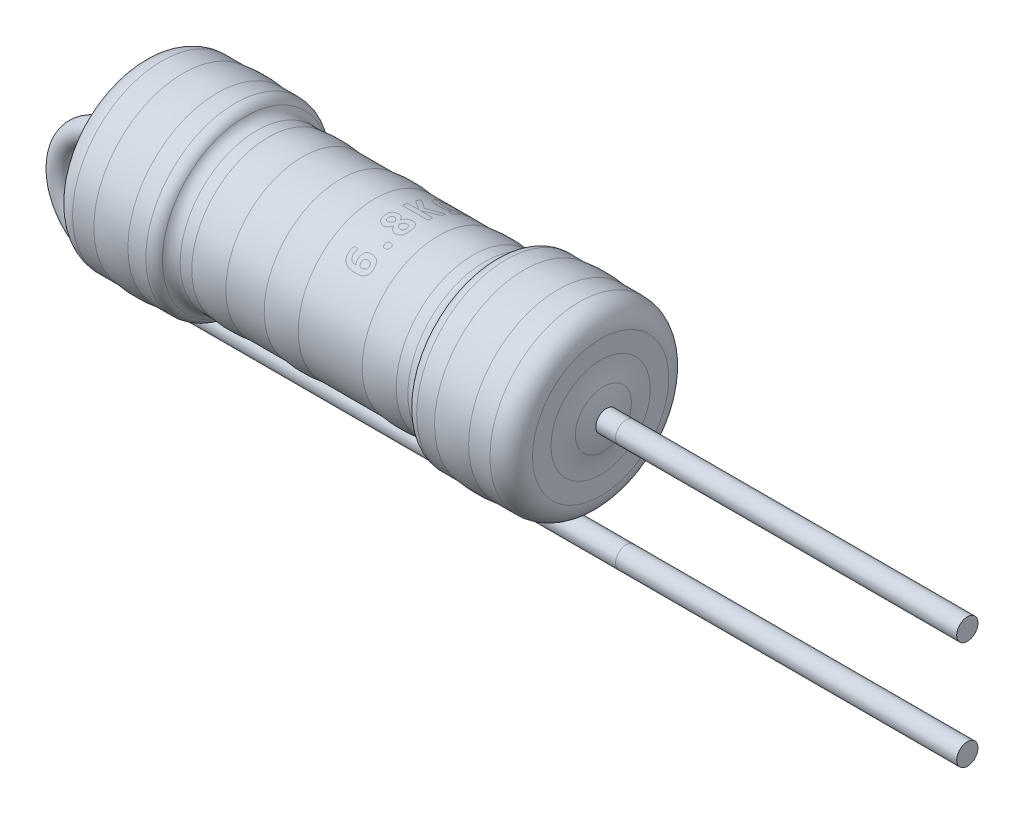
SolidWorks part; units mm, degrees
ref_plane "Front Plane" through (0, 0, 0) normal (0, 0, 1) x (1, 0, 0)
ref_plane "Top Plane" through (0, 0, 0) normal (0, 1, 0) x (1, 0, 0)
ref_plane "Right Plane" through (0, 0, 0) normal (1, 0, 0) x (0, 0, -1)
sketch "Sketch Set Wire Width" plane through (0, 0, 0) normal (0, 0, 1) x (1, 0, 0)
  line L0 (0, 0) -> (6, 0)
  line L1 (6, -2.54) -> (-6, -2.54)
  line L2 (6, 0) -> (14.0102, 0)
  line L3 (-6, 0) -> (-6, -2.54) construction
  line L4 (-6, 0) -> (-6, -2.54) construction
  line L5 (6, -2.54) -> (6, 0) construction
  line L6 (6, -2.54) -> (14.0102, -2.54)
  line L7 (14.0102, -2.54) -> (14.0102, 0) construction
  line L8 (-6, 0) -> (0, 0)
  arc A0 (-6, 0) -> (-6, -2.54) centre (-6, -1.27) ccw
  dimension "D2" = 2.54
  dimension "D3" = 30
  dimension "D1" = 12
  dimension "D4" = 6
sketch "Sketch Wire Diameter" plane through (0, 0, 0) normal (1, 0, 0) x (0, 0, -1)
  circle A0 centre (0, 0) radius 0.25
  dimension "D1" = 0.5
sweep "SET WIRE LENGTH" add profiles "Sketch Wire Diameter" path "Sketch Set Wire Width"
sketch "Sketch3" plane through (0, 0, 0) normal (0, 0, 1) x (1, 0, 0)
  line L0 (-5.4, 0) -> (5.4, 0)
  line L1 (0, 0) -> (0, 1.8) construction
  line L2 (-2.9, 1.8) -> (2.9, 1.8)
  line L3 (-5.4, 0) -> (-5.4, 1.6)
  line L4 (-4.9, 2.1) -> (-3.18, 2.1)
  line L5 (-2.9, 1.82) -> (-2.9, 1.8)
  line L6 (5.4, 0) -> (5.4, 1.6)
  line L7 (4.9, 2.1) -> (3.18, 2.1)
  line L8 (2.9, 1.82) -> (2.9, 1.8)
  arc A0 (-5.4, 1.6) -> (-4.9, 2.1) centre (-4.9, 1.6) cw
  arc A1 (5.4, 1.6) -> (4.9, 2.1) centre (4.9, 1.6) ccw
  arc A2 (-3.18, 2.1) -> (-2.9, 1.82) centre (-3.18, 1.82) cw
  arc A3 (3.18, 2.1) -> (2.9, 1.82) centre (3.18, 1.82) ccw
  dimension "D5" = 0.5
  dimension "D6" = 0.28
  dimension "D1" = 10.8
  dimension "D2" = 5.8
  dimension "D3" = 1.8
  dimension "D4" = 2.1
revolve "Revolve2" add sketch "Sketch3" angle 360 about L0
fillet "Fillet1" radius 0.3 2 edges at (2.9, 0, 1.8) (-2.9, 0, 1.8)
sketch "Sketch5" plane through (0, 0, 0) normal (0, 0, 1) x (1, 0, 0)
  line L0 (0, 0) -> (2, 0) construction
  line L1 (0, 0) -> (-0.3, 0) construction
  line L2 (-0.3, 0) -> (-2, 0) construction
  line L3 (-2, 0) -> (-4, 0) construction
  line L4 (2, 0) -> (4, 0) construction
  line L5 (-4, 0) -> (-4, 2.1) construction
  line L6 (-0.3, 0) -> (-0.3, 1.8) construction
  line L7 (-2, 0) -> (-2, 1.8) construction
  line L8 (2, 0) -> (2, 1.8) construction
  line L9 (4, 0) -> (4, 2.1) construction
  line L10 (-4, 2.1) -> (-4, 2.13) construction
  line L11 (-4.9, 2.1) -> (-3.18, 2.1) construction
  line L12 (4.9, 2.1) -> (3.18, 2.1) construction
  line L13 (-2.9, 1.8) -> (2.9, 1.8) construction
  line L14 (-2, 1.8) -> (-2, 1.83) construction
  line L17 (-4.4, 2.1) -> (-3.6, 2.1)
  line L19 (-5.4, 0) -> (5.4, 0) construction
  line L22 (-2.4, 1.8) -> (-1.6, 1.8) construction
  line L26 (-0.7, 1.8) -> (0.1, 1.8) construction
  line L30 (1.6, 1.8) -> (2.4, 1.8) construction
  line L34 (3.6, 2.1) -> (4.4, 2.1) construction
  line L36 (-0.3, 1.8) -> (-0.3, 1.83) construction
  line L37 (2, 1.8) -> (2, 1.83) construction
  line L38 (4, 2.1) -> (4, 2.13) construction
  arc A0 (-4.4, 2.1) -> (-3.6, 2.1) centre (-4, -0.5517) cw
  arc A1 (-2.4, 1.8) -> (-1.6, 1.8) centre (-2, -0.8517) cw construction
  arc A2 (-0.7, 1.8) -> (0.1, 1.8) centre (-0.3, -0.8517) cw construction
  arc A3 (1.6, 1.8) -> (2.4, 1.8) centre (2, -0.8517) cw construction
  arc A4 (3.6, 2.1) -> (4.4, 2.1) centre (4, -0.5517) cw construction
  dimension "D3" = 0.8
  dimension "D1" = 4
  dimension "D2" = 4
  dimension "D4" = 0.03
  dimension "D5" = 2
  dimension "D6" = 2
  dimension "D7" = 1.7
revolve "Band 1" add sketch "Sketch5" angle 360 about L2
sketch "Sketch8" plane through (0, 0, 0) normal (0, 0, 1) x (1, 0, 0)
  line L0 (-2.4, 1.8) -> (-1.6, 1.8) construction
  line L1 (-2.4, 1.8) -> (-1.6, 1.8)
  arc A0 (-1.6, 1.8) -> (-2.4, 1.8) centre (-2, -0.8517) ccw construction
  arc A1 (-1.6, 1.8) -> (-2.4, 1.8) centre (-2, -0.8517) ccw
revolve "Band 2" add sketch "Sketch8" angle 360 about L2
sketch "Sketch9" plane through (0, 0, 0) normal (0, 0, 1) x (1, 0, 0)
  line L0 (-0.7, 1.8) -> (0.1, 1.8) construction
  line L1 (-0.7, 1.8) -> (0.1, 1.8)
  arc A0 (0.1, 1.8) -> (-0.7, 1.8) centre (-0.3, -0.8517) ccw construction
  arc A1 (0.1, 1.8) -> (-0.7, 1.8) centre (-0.3, -0.8517) ccw
revolve "Band 3" add sketch "Sketch9" angle 360 about L2
sketch "Sketch10" plane through (0, 0, 0) normal (0, 0, 1) x (1, 0, 0)
  line L0 (1.6, 1.8) -> (2.4, 1.8) construction
  line L1 (1.6, 1.8) -> (2.4, 1.8)
  arc A0 (2.4, 1.8) -> (1.6, 1.8) centre (2, -0.8517) ccw construction
  arc A1 (2.4, 1.8) -> (1.6, 1.8) centre (2, -0.8517) ccw
revolve "Band 4" add sketch "Sketch10" angle 360 about L0
sketch "Sketch11" plane through (0, 0, 0) normal (0, 0, 1) x (1, 0, 0)
  line L0 (3.6, 2.1) -> (4.4, 2.1) construction
  line L1 (3.6, 2.1) -> (4.4, 2.1)
  arc A0 (4.4, 2.1) -> (3.6, 2.1) centre (4, -0.5517) ccw construction
  arc A1 (4.4, 2.1) -> (3.6, 2.1) centre (4, -0.5517) ccw
revolve "Band 5" add sketch "Sketch11" angle 360 about L4
sketch "Sketch12" plane through (0, 0, 0) normal (0, 0, 1) x (1, 0, 0)
  line L0 (-5.35, 0) -> (5.35, 0) construction
  line L1 (-5.35, 1) -> (-5.35, 0)
  line L2 (5.35, 1) -> (5.35, 0)
  line L3 (-5.35, 0) -> (-5.55, 0)
  line L4 (5.35, 0) -> (5.55, 0)
  arc A0 (-5.35, 1) -> (-5.55, 0) centre (-2.95, 0) ccw
  arc A1 (5.35, 1) -> (5.55, 0) centre (2.95, 0) cw
  dimension "D3" = 0.2
  dimension "D4" = 2.6
  dimension "D1" = 10.7
  dimension "D2" = 1
revolve "Revolve10" add sketch "Sketch12" angle 360 about L0
fillet "Fillet2" radius 2 2 edges at (5.4, 0, 0.8703) (-5.4, 0, -0.8703)
ref_plane "Plane2" through (0, 3, 0) normal (0, 1, 0) x (1, 0, 0)
sketch "Sketch13" plane through (0, 3, 0) normal (0, 1, 0) x (1, 0, 0)
  line L0 (0, 0) -> (1.15, 0) construction
  line L1 (1.15, 1.75) -> (1.15, -1.75) construction
  text T0 "6.8KΩ" font "Calibri" height 0.6
  dimension "D1" = 3.5
  dimension "D2" = 1.15
wrap "Wrap1" sketch "Sketch13" wrap type scribe source sketch "Sketch13" face at (0.1, 1.8, 0)
